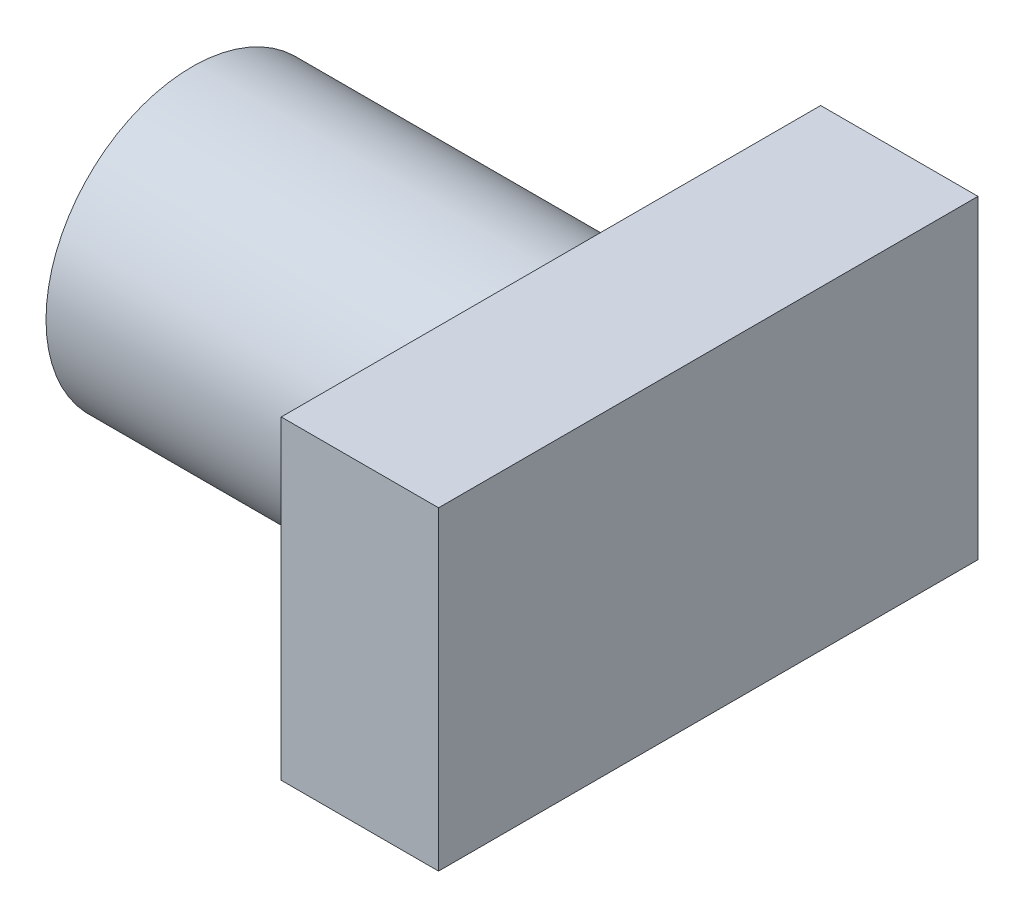
SolidWorks part; units mm, degrees
ref_plane "Front Plane" through (0, 0, 0) normal (0, 0, 1) x (1, 0, 0)
ref_plane "Top Plane" through (0, 0, 0) normal (0, 1, 0) x (1, 0, 0)
ref_plane "Right Plane" through (0, 0, 0) normal (1, 0, 0) x (0, 0, -1)
sketch "Sketch1" plane through (0, 0, 0) normal (0, 1, 0) x (1, 0, 0)
  line L1 (0, 0) -> (35, 0)
  line L2 (0, 0) -> (0, 120)
  line L3 (0, 120) -> (35, 120)
  line L4 (35, 0) -> (35, 120)
  dimension "D1" = 120
  dimension "D2" = 35
extrude "Boss-Extrude1" add sketch "Sketch1" along normal blind 70 contours L4 L3 L2 L1
sketch "Sketch2" plane through (0, 0, 0) normal (-1, 0, 0) x (0, 0, 1)
  circle A0 centre (-60.1749, 34.8908) radius 32.5
  dimension "D1" = 65
extrude "Boss-Extrude2" add sketch "Sketch2" along normal blind 80
